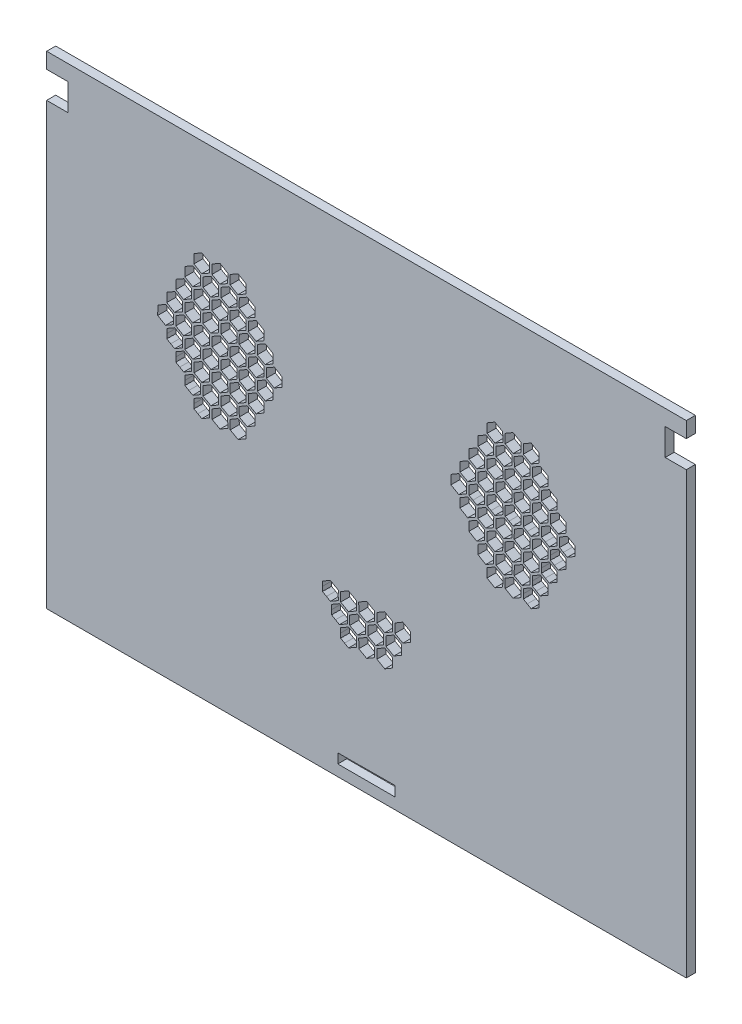
SolidWorks part; units mm, degrees
ref_plane "Front Plane" through (0, 0, 0) normal (0, 0, 1) x (1, 0, 0)
ref_plane "Top Plane" through (0, 0, 0) normal (0, 1, 0) x (1, 0, 0)
ref_plane "Right Plane" through (0, 0, 0) normal (1, 0, 0) x (0, 0, -1)
sketch "Sketch1" plane through (0, 0, 0) normal (0, 0, 1) x (1, 0, 0)
  line L0 (-106, 80) -> (-106, 74.8)
  line L1 (106, -80) -> (-106, -80)
  line L2 (106, -80) -> (106, 65.9)
  line L3 (106, 80) -> (-106, 80)
  line L4 (-106, -80) -> (-106, 65.9)
  line L5 (106, -80) -> (-106, 80) construction
  line L6 (106, 80) -> (-106, -80) construction
  line L8 (-106, 74.8) -> (-99, 74.8)
  line L10 (-106, 65.9) -> (-99, 65.9)
  line L11 (-99, 74.8) -> (-99, 65.9)
  line L12 (106, 65.9) -> (99, 65.9)
  line L13 (99, 74.8) -> (99, 65.9)
  line L14 (106, 74.8) -> (99, 74.8)
  line L15 (-106, 74.8) -> (-106, 80)
  line L16 (106, 74.8) -> (106, 80)
  line L18 (9.5, -73) -> (-9.5, -73.1166)
  line L19 (-2.0199, -73.1166) -> (-10.0199, -73.1166) construction
  line L20 (-9.5, -73.1166) -> (-9.5, -76.3166)
  line L21 (-9.5, -76.3166) -> (9.5, -76.3166)
  line L22 (9.5, -73) -> (9.5, -76.3166)
  line L275 (0, 24.0494) -> (50, 24.0494)
  line L276 (50, 24.0494) -> (-50, 24.0494)
  line L278 (0, 0) -> (0, 24.0494)
  line L284 (0, 24.0494) -> (-31.8655, 24.0494)
  line L290 (-31.8655, 24.0494) -> (31.8655, 24.0494)
  line L328 (-17.2944, 13.0523) -> (-57.2944, 43.241) construction
  line L337 (69.1585, 25.5708) -> (66.5481, 27.0493)
  line L354 (15.6596, 11.8186) -> (63.8404, 48.1814) construction
  line L355 (63.9873, 22.528) -> (66.5977, 21.0495)
  line L628 (-9.3462, -29.3321) -> (-9.371, -26.3322)
  line L629 (66.5977, 21.0495) -> (69.1833, 22.5709)
  line L630 (69.1833, 22.5709) -> (69.1585, 25.5708)
  line L631 (66.5481, 27.0493) -> (63.9625, 25.5279)
  line L632 (63.9625, 25.5279) -> (63.9873, 22.528)
  line L633 (57.9625, 25.5279) -> (57.9873, 22.528)
  line L638 (30, 4.0494) -> (70, 44.0494) construction
  line L639 (30, 44.0494) -> (70, 4.0494) construction
  line L640 (60.5481, 27.0493) -> (57.9625, 25.5279)
  line L641 (63.1585, 25.5708) -> (60.5481, 27.0493)
  line L642 (63.1833, 22.5709) -> (63.1585, 25.5708)
  line L643 (60.5977, 21.0495) -> (63.1833, 22.5709)
  line L644 (57.9873, 22.528) -> (60.5977, 21.0495)
  line L645 (51.9625, 25.5279) -> (51.9873, 22.528)
  line L646 (54.5481, 27.0493) -> (51.9625, 25.5279)
  line L647 (57.1585, 25.5708) -> (54.5481, 27.0493)
  line L648 (57.1833, 22.5709) -> (57.1585, 25.5708)
  line L649 (54.5977, 21.0495) -> (57.1833, 22.5709)
  line L650 (51.9873, 22.528) -> (54.5977, 21.0495)
  line L651 (45.9625, 25.5279) -> (45.9873, 22.528)
  line L652 (48.5481, 27.0493) -> (45.9625, 25.5279)
  line L653 (51.1585, 25.5708) -> (48.5481, 27.0493)
  line L654 (51.1833, 22.5709) -> (51.1585, 25.5708)
  line L655 (48.5977, 21.0495) -> (51.1833, 22.5709)
  line L656 (45.9873, 22.528) -> (48.5977, 21.0495)
  line L657 (39.9625, 25.5279) -> (39.9873, 22.528)
  line L658 (42.5481, 27.0493) -> (39.9625, 25.5279)
  line L659 (45.1585, 25.5708) -> (42.5481, 27.0493)
  line L660 (45.1833, 22.5709) -> (45.1585, 25.5708)
  line L661 (42.5977, 21.0495) -> (45.1833, 22.5709)
  line L662 (39.9873, 22.528) -> (42.5977, 21.0495)
  line L663 (33.9625, 25.5279) -> (33.9873, 22.528)
  line L664 (36.5481, 27.0493) -> (33.9625, 25.5279)
  line L665 (39.1585, 25.5708) -> (36.5481, 27.0493)
  line L666 (39.1833, 22.5709) -> (39.1585, 25.5708)
  line L667 (36.5977, 21.0495) -> (39.1833, 22.5709)
  line L668 (33.9873, 22.528) -> (36.5977, 21.0495)
  line L669 (27.9625, 25.5279) -> (27.9873, 22.528)
  line L670 (30.5481, 27.0493) -> (27.9625, 25.5279)
  line L671 (33.1585, 25.5708) -> (30.5481, 27.0493)
  line L672 (33.1833, 22.5709) -> (33.1585, 25.5708)
  line L673 (30.5977, 21.0495) -> (33.1833, 22.5709)
  line L674 (27.9873, 22.528) -> (30.5977, 21.0495)
  line L675 (60.9625, 30.7241) -> (60.9873, 27.7242)
  line L676 (63.5481, 32.2455) -> (60.9625, 30.7241)
  line L677 (66.1585, 30.767) -> (63.5481, 32.2455)
  line L678 (66.1833, 27.7671) -> (66.1585, 30.767)
  line L679 (63.5977, 26.2457) -> (66.1833, 27.7671)
  line L680 (60.9873, 27.7242) -> (63.5977, 26.2457)
  line L681 (57.9625, 35.9202) -> (57.9873, 32.9203)
  line L682 (60.5481, 37.4416) -> (57.9625, 35.9202)
  line L683 (63.1585, 35.9631) -> (60.5481, 37.4416)
  line L684 (63.1833, 32.9632) -> (63.1585, 35.9631)
  line L685 (60.5977, 31.4418) -> (63.1833, 32.9632)
  line L686 (57.9873, 32.9203) -> (60.5977, 31.4418)
  line L687 (54.9625, 41.1164) -> (54.9873, 38.1165)
  line L688 (57.5481, 42.6378) -> (54.9625, 41.1164)
  line L689 (60.1585, 41.1593) -> (57.5481, 42.6378)
  line L690 (60.1833, 38.1594) -> (60.1585, 41.1593)
  line L691 (57.5977, 36.638) -> (60.1833, 38.1594)
  line L692 (54.9873, 38.1165) -> (57.5977, 36.638)
  line L693 (60.9625, 20.3318) -> (60.9873, 17.3319)
  line L694 (63.5481, 21.8532) -> (60.9625, 20.3318)
  line L695 (66.1585, 20.3747) -> (63.5481, 21.8532)
  line L696 (66.1833, 17.3748) -> (66.1585, 20.3747)
  line L697 (63.5977, 15.8534) -> (66.1833, 17.3748)
  line L698 (60.9873, 17.3319) -> (63.5977, 15.8534)
  line L699 (57.9625, 15.1356) -> (57.9873, 12.1357)
  line L700 (60.5481, 16.657) -> (57.9625, 15.1356)
  line L701 (63.1585, 15.1785) -> (60.5481, 16.657)
  line L702 (63.1833, 12.1786) -> (63.1585, 15.1785)
  line L703 (60.5977, 10.6572) -> (63.1833, 12.1786)
  line L704 (57.9873, 12.1357) -> (60.5977, 10.6572)
  line L705 (54.9625, 9.9395) -> (54.9873, 6.9396)
  line L706 (57.5481, 11.4609) -> (54.9625, 9.9395)
  line L707 (60.1585, 9.9824) -> (57.5481, 11.4609)
  line L708 (60.1833, 6.9825) -> (60.1585, 9.9824)
  line L709 (57.5977, 5.4611) -> (60.1833, 6.9825)
  line L710 (54.9873, 6.9396) -> (57.5977, 5.4611)
  line L711 (51.9625, 4.7433) -> (51.9873, 1.7434)
  line L712 (54.5481, 6.2647) -> (51.9625, 4.7433)
  line L713 (57.1585, 4.7862) -> (54.5481, 6.2647)
  line L714 (57.1833, 1.7863) -> (57.1585, 4.7862)
  line L715 (54.5977, 0.2649) -> (57.1833, 1.7863)
  line L716 (51.9873, 1.7434) -> (54.5977, 0.2649)
  line L717 (60.9625, 30.7241) -> (60.9873, 27.7242)
  line L718 (63.5481, 32.2455) -> (60.9625, 30.7241)
  line L719 (66.1585, 30.767) -> (63.5481, 32.2455)
  line L720 (66.1833, 27.7671) -> (66.1585, 30.767)
  line L721 (63.5977, 26.2457) -> (66.1833, 27.7671)
  line L722 (60.9873, 27.7242) -> (63.5977, 26.2457)
  line L723 (57.9625, 35.9202) -> (57.9873, 32.9203)
  line L724 (60.5481, 37.4416) -> (57.9625, 35.9202)
  line L725 (63.1585, 35.9631) -> (60.5481, 37.4416)
  line L726 (63.1833, 32.9632) -> (63.1585, 35.9631)
  line L727 (60.5977, 31.4418) -> (63.1833, 32.9632)
  line L728 (57.9873, 32.9203) -> (60.5977, 31.4418)
  line L729 (54.9625, 41.1164) -> (54.9873, 38.1165)
  line L730 (57.5481, 42.6378) -> (54.9625, 41.1164)
  line L731 (60.1585, 41.1593) -> (57.5481, 42.6378)
  line L732 (60.1833, 38.1594) -> (60.1585, 41.1593)
  line L733 (57.5977, 36.638) -> (60.1833, 38.1594)
  line L734 (54.9873, 38.1165) -> (57.5977, 36.638)
  line L735 (51.9625, 46.3125) -> (51.9873, 43.3126)
  line L736 (54.5481, 47.8339) -> (51.9625, 46.3125)
  line L737 (57.1585, 46.3554) -> (54.5481, 47.8339)
  line L738 (57.1833, 43.3555) -> (57.1585, 46.3554)
  line L739 (54.5977, 41.8341) -> (57.1833, 43.3555)
  line L740 (51.9873, 43.3126) -> (54.5977, 41.8341)
  line L741 (57.5977, 26.2457) -> (60.1833, 27.7671)
  line L742 (54.9873, 27.7242) -> (57.5977, 26.2457)
  line L743 (54.9625, 30.7241) -> (54.9873, 27.7242)
  line L744 (57.5481, 32.2455) -> (54.9625, 30.7241)
  line L745 (60.1585, 30.767) -> (57.5481, 32.2455)
  line L746 (60.1833, 27.7671) -> (60.1585, 30.767)
  line L747 (51.5977, 26.2457) -> (54.1833, 27.7671)
  line L748 (48.9873, 27.7242) -> (51.5977, 26.2457)
  line L749 (48.9625, 30.7241) -> (48.9873, 27.7242)
  line L750 (51.5481, 32.2455) -> (48.9625, 30.7241)
  line L751 (54.1585, 30.767) -> (51.5481, 32.2455)
  line L752 (54.1833, 27.7671) -> (54.1585, 30.767)
  line L753 (45.5977, 26.2457) -> (48.1833, 27.7671)
  line L754 (42.9873, 27.7242) -> (45.5977, 26.2457)
  line L755 (42.9625, 30.7241) -> (42.9873, 27.7242)
  line L756 (45.5481, 32.2455) -> (42.9625, 30.7241)
  line L757 (48.1585, 30.767) -> (45.5481, 32.2455)
  line L758 (48.1833, 27.7671) -> (48.1585, 30.767)
  line L759 (39.5977, 26.2457) -> (42.1833, 27.7671)
  line L760 (36.9873, 27.7242) -> (39.5977, 26.2457)
  line L761 (36.9625, 30.7241) -> (36.9873, 27.7242)
  line L762 (39.5481, 32.2455) -> (36.9625, 30.7241)
  line L763 (42.1585, 30.767) -> (39.5481, 32.2455)
  line L764 (42.1833, 27.7671) -> (42.1585, 30.767)
  line L765 (33.5977, 26.2457) -> (36.1833, 27.7671)
  line L766 (30.9873, 27.7242) -> (33.5977, 26.2457)
  line L767 (30.9625, 30.7241) -> (30.9873, 27.7242)
  line L768 (33.5481, 32.2455) -> (30.9625, 30.7241)
  line L769 (36.1585, 30.767) -> (33.5481, 32.2455)
  line L770 (36.1833, 27.7671) -> (36.1585, 30.767)
  line L771 (57.5977, 26.2457) -> (60.1833, 27.7671)
  line L772 (54.9873, 27.7242) -> (57.5977, 26.2457)
  line L773 (54.9625, 30.7241) -> (54.9873, 27.7242)
  line L774 (57.5481, 32.2455) -> (54.9625, 30.7241)
  line L775 (60.1585, 30.767) -> (57.5481, 32.2455)
  line L776 (60.1833, 27.7671) -> (60.1585, 30.767)
  line L777 (54.5481, 37.4416) -> (51.9625, 35.9202)
  line L778 (51.9625, 35.9202) -> (51.9873, 32.9203)
  line L779 (51.9873, 32.9203) -> (54.5977, 31.4418)
  line L780 (54.5977, 31.4418) -> (57.1833, 32.9632)
  line L781 (57.1833, 32.9632) -> (57.1585, 35.9631)
  line L782 (57.1585, 35.9631) -> (54.5481, 37.4416)
  line L783 (48.9873, 38.1165) -> (51.5977, 36.638)
  line L784 (48.9625, 41.1164) -> (48.9873, 38.1165)
  line L785 (51.5481, 42.6378) -> (48.9625, 41.1164)
  line L786 (54.1585, 41.1593) -> (51.5481, 42.6378)
  line L787 (54.1833, 38.1594) -> (54.1585, 41.1593)
  line L788 (51.5977, 36.638) -> (54.1833, 38.1594)
  line L789 (45.9873, 43.3126) -> (48.5977, 41.8341)
  line L790 (45.9625, 46.3125) -> (45.9873, 43.3126)
  line L791 (48.5481, 47.8339) -> (45.9625, 46.3125)
  line L792 (51.1585, 46.3554) -> (48.5481, 47.8339)
  line L793 (51.1833, 43.3555) -> (51.1585, 46.3554)
  line L794 (48.5977, 41.8341) -> (51.1833, 43.3555)
  line L795 (51.5977, 26.2457) -> (54.1833, 27.7671)
  line L796 (48.9873, 27.7242) -> (51.5977, 26.2457)
  line L797 (48.9625, 30.7241) -> (48.9873, 27.7242)
  line L798 (51.5481, 32.2455) -> (48.9625, 30.7241)
  line L799 (54.1585, 30.767) -> (51.5481, 32.2455)
  line L800 (54.1833, 27.7671) -> (54.1585, 30.767)
  line L801 (48.5481, 37.4416) -> (45.9625, 35.9202)
  line L802 (45.9625, 35.9202) -> (45.9873, 32.9203)
  line L803 (45.9873, 32.9203) -> (48.5977, 31.4418)
  line L804 (48.5977, 31.4418) -> (51.1833, 32.9632)
  line L805 (51.1833, 32.9632) -> (51.1585, 35.9631)
  line L806 (51.1585, 35.9631) -> (48.5481, 37.4416)
  line L807 (42.9873, 38.1165) -> (45.5977, 36.638)
  line L808 (42.9625, 41.1164) -> (42.9873, 38.1165)
  line L809 (45.5481, 42.6378) -> (42.9625, 41.1164)
  line L810 (48.1585, 41.1593) -> (45.5481, 42.6378)
  line L811 (48.1833, 38.1594) -> (48.1585, 41.1593)
  line L812 (45.5977, 36.638) -> (48.1833, 38.1594)
  line L813 (39.9873, 43.3126) -> (42.5977, 41.8341)
  line L814 (39.9625, 46.3125) -> (39.9873, 43.3126)
  line L815 (42.5481, 47.8339) -> (39.9625, 46.3125)
  line L816 (45.1585, 46.3554) -> (42.5481, 47.8339)
  line L817 (45.1833, 43.3555) -> (45.1585, 46.3554)
  line L818 (42.5977, 41.8341) -> (45.1833, 43.3555)
  line L819 (45.5977, 26.2457) -> (48.1833, 27.7671)
  line L820 (42.9873, 27.7242) -> (45.5977, 26.2457)
  line L821 (42.9625, 30.7241) -> (42.9873, 27.7242)
  line L822 (45.5481, 32.2455) -> (42.9625, 30.7241)
  line L823 (48.1585, 30.767) -> (45.5481, 32.2455)
  line L824 (48.1833, 27.7671) -> (48.1585, 30.767)
  line L825 (42.5481, 37.4416) -> (39.9625, 35.9202)
  line L826 (39.9625, 35.9202) -> (39.9873, 32.9203)
  line L827 (39.9873, 32.9203) -> (42.5977, 31.4418)
  line L828 (42.5977, 31.4418) -> (45.1833, 32.9632)
  line L829 (45.1833, 32.9632) -> (45.1585, 35.9631)
  line L830 (45.1585, 35.9631) -> (42.5481, 37.4416)
  line L831 (36.9873, 38.1165) -> (39.5977, 36.638)
  line L832 (36.9625, 41.1164) -> (36.9873, 38.1165)
  line L833 (39.5481, 42.6378) -> (36.9625, 41.1164)
  line L834 (42.1585, 41.1593) -> (39.5481, 42.6378)
  line L835 (42.1833, 38.1594) -> (42.1585, 41.1593)
  line L836 (39.5977, 36.638) -> (42.1833, 38.1594)
  line L843 (39.5977, 26.2457) -> (42.1833, 27.7671)
  line L844 (36.9873, 27.7242) -> (39.5977, 26.2457)
  line L845 (36.9625, 30.7241) -> (36.9873, 27.7242)
  line L846 (39.5481, 32.2455) -> (36.9625, 30.7241)
  line L847 (42.1585, 30.767) -> (39.5481, 32.2455)
  line L848 (42.1833, 27.7671) -> (42.1585, 30.767)
  line L849 (36.5481, 37.4416) -> (33.9625, 35.9202)
  line L850 (33.9625, 35.9202) -> (33.9873, 32.9203)
  line L851 (33.9873, 32.9203) -> (36.5977, 31.4418)
  line L852 (36.5977, 31.4418) -> (39.1833, 32.9632)
  line L853 (39.1833, 32.9632) -> (39.1585, 35.9631)
  line L854 (39.1585, 35.9631) -> (36.5481, 37.4416)
  line L867 (33.9873, 43.3126) -> (36.5977, 41.8341) [skipped]
  line L868 (33.9625, 46.3125) -> (33.9873, 43.3126) [skipped]
  line L869 (36.5481, 47.8339) -> (33.9625, 46.3125) [skipped]
  line L870 (27.9873, 43.3126) -> (30.5977, 41.8341) [skipped]
  line L871 (27.9625, 46.3125) -> (27.9873, 43.3126) [skipped]
  line L872 (30.5481, 47.8339) -> (27.9625, 46.3125) [skipped]
  line L873 (33.1585, 46.3554) -> (30.5481, 47.8339) [skipped]
  line L874 (33.1833, 43.3555) -> (33.1585, 46.3554) [skipped]
  line L875 (30.5977, 41.8341) -> (33.1833, 43.3555) [skipped]
  line L876 (39.1585, 46.3554) -> (36.5481, 47.8339) [skipped]
  line L877 (36.5977, 41.8341) -> (39.1833, 43.3555) [skipped]
  line L878 (39.1833, 43.3555) -> (39.1585, 46.3554) [skipped]
  line L879 (36.1585, 41.1593) -> (33.5481, 42.6378) [skipped]
  line L880 (33.5481, 42.6378) -> (30.9625, 41.1164) [skipped]
  line L881 (30.9625, 41.1164) -> (30.9873, 38.1165) [skipped]
  line L882 (30.9873, 38.1165) -> (33.5977, 36.638) [skipped]
  line L883 (33.5977, 36.638) -> (36.1833, 38.1594) [skipped]
  line L884 (36.1833, 38.1594) -> (36.1585, 41.1593) [skipped]
  line L885 (39.1585, 12.1357) -> (36.5481, 10.6572)
  line L886 (39.1833, 15.1356) -> (39.1585, 12.1357)
  line L887 (36.5977, 16.657) -> (39.1833, 15.1356)
  line L888 (33.9873, 15.1785) -> (36.5977, 16.657)
  line L889 (33.9625, 12.1786) -> (33.9873, 15.1785)
  line L890 (36.5481, 10.6572) -> (33.9625, 12.1786)
  line L891 (42.1833, 20.3318) -> (42.1585, 17.3319)
  line L892 (42.1585, 17.3319) -> (39.5481, 15.8534)
  line L893 (39.5481, 15.8534) -> (36.9625, 17.3748)
  line L894 (36.9625, 17.3748) -> (36.9873, 20.3747)
  line L895 (36.9873, 20.3747) -> (39.5977, 21.8532)
  line L896 (39.5977, 21.8532) -> (42.1833, 20.3318)
  line L897 (39.5977, 11.4609) -> (42.1833, 9.9395)
  line L898 (42.1833, 9.9395) -> (42.1585, 6.9396)
  line L899 (42.1585, 6.9396) -> (39.5481, 5.4611)
  line L900 (39.5481, 5.4611) -> (36.9625, 6.9825)
  line L901 (36.9625, 6.9825) -> (36.9873, 9.9824)
  line L902 (36.9873, 9.9824) -> (39.5977, 11.4609)
  line L903 (45.1585, 12.1357) -> (42.5481, 10.6572)
  line L904 (45.1833, 15.1356) -> (45.1585, 12.1357)
  line L905 (42.5977, 16.657) -> (45.1833, 15.1356)
  line L906 (39.9873, 15.1785) -> (42.5977, 16.657)
  line L907 (39.9625, 12.1786) -> (39.9873, 15.1785)
  line L908 (42.5481, 10.6572) -> (39.9625, 12.1786)
  line L909 (48.1833, 20.3318) -> (48.1585, 17.3319)
  line L910 (48.1585, 17.3319) -> (45.5481, 15.8534)
  line L911 (45.5481, 15.8534) -> (42.9625, 17.3748)
  line L912 (42.9625, 17.3748) -> (42.9873, 20.3747)
  line L913 (42.9873, 20.3747) -> (45.5977, 21.8532)
  line L914 (45.5977, 21.8532) -> (48.1833, 20.3318)
  line L915 (42.5977, 6.2647) -> (45.1833, 4.7433)
  line L916 (45.1833, 4.7433) -> (45.1585, 1.7434)
  line L917 (45.1585, 1.7434) -> (42.5481, 0.2649)
  line L918 (42.5481, 0.2649) -> (39.9625, 1.7863)
  line L919 (39.9625, 1.7863) -> (39.9873, 4.7862)
  line L920 (39.9873, 4.7862) -> (42.5977, 6.2647)
  line L921 (45.5977, 11.4609) -> (48.1833, 9.9395)
  line L922 (48.1833, 9.9395) -> (48.1585, 6.9396)
  line L923 (48.1585, 6.9396) -> (45.5481, 5.4611)
  line L924 (45.5481, 5.4611) -> (42.9625, 6.9825)
  line L925 (42.9625, 6.9825) -> (42.9873, 9.9824)
  line L926 (42.9873, 9.9824) -> (45.5977, 11.4609)
  line L927 (51.1585, 12.1357) -> (48.5481, 10.6572)
  line L928 (51.1833, 15.1356) -> (51.1585, 12.1357)
  line L929 (48.5977, 16.657) -> (51.1833, 15.1356)
  line L930 (45.9873, 15.1785) -> (48.5977, 16.657)
  line L931 (45.9625, 12.1786) -> (45.9873, 15.1785)
  line L932 (48.5481, 10.6572) -> (45.9625, 12.1786)
  line L933 (54.1833, 20.3318) -> (54.1585, 17.3319)
  line L934 (54.1585, 17.3319) -> (51.5481, 15.8534)
  line L935 (51.5481, 15.8534) -> (48.9625, 17.3748)
  line L936 (48.9625, 17.3748) -> (48.9873, 20.3747)
  line L937 (48.9873, 20.3747) -> (51.5977, 21.8532)
  line L938 (51.5977, 21.8532) -> (54.1833, 20.3318)
  line L939 (48.5977, 6.2647) -> (51.1833, 4.7433)
  line L940 (51.1833, 4.7433) -> (51.1585, 1.7434)
  line L941 (51.1585, 1.7434) -> (48.5481, 0.2649)
  line L942 (48.5481, 0.2649) -> (45.9625, 1.7863)
  line L943 (45.9625, 1.7863) -> (45.9873, 4.7862)
  line L944 (45.9873, 4.7862) -> (48.5977, 6.2647)
  line L945 (51.5977, 11.4609) -> (54.1833, 9.9395)
  line L946 (54.1833, 9.9395) -> (54.1585, 6.9396)
  line L947 (54.1585, 6.9396) -> (51.5481, 5.4611)
  line L948 (51.5481, 5.4611) -> (48.9625, 6.9825)
  line L949 (48.9625, 6.9825) -> (48.9873, 9.9824)
  line L950 (48.9873, 9.9824) -> (51.5977, 11.4609)
  line L951 (57.1585, 12.1357) -> (54.5481, 10.6572)
  line L952 (57.1833, 15.1356) -> (57.1585, 12.1357)
  line L953 (54.5977, 16.657) -> (57.1833, 15.1356)
  line L954 (51.9873, 15.1785) -> (54.5977, 16.657)
  line L955 (51.9625, 12.1786) -> (51.9873, 15.1785)
  line L956 (54.5481, 10.6572) -> (51.9625, 12.1786)
  line L957 (60.1833, 20.3318) -> (60.1585, 17.3319)
  line L958 (60.1585, 17.3319) -> (57.5481, 15.8534)
  line L959 (57.5481, 15.8534) -> (54.9625, 17.3748)
  line L960 (54.9625, 17.3748) -> (54.9873, 20.3747)
  line L961 (54.9873, 20.3747) -> (57.5977, 21.8532)
  line L962 (57.5977, 21.8532) -> (60.1833, 20.3318)
  line L963 (36.1833, 20.3318) -> (36.1585, 17.3319)
  line L964 (36.1585, 17.3319) -> (33.5481, 15.8534)
  line L965 (33.5481, 15.8534) -> (30.9625, 17.3748)
  line L966 (30.9625, 17.3748) -> (30.9873, 20.3747)
  line L967 (30.9873, 20.3747) -> (33.5977, 21.8532)
  line L968 (33.5977, 21.8532) -> (36.1833, 20.3318)
  line L969 (42.1833, 20.3318) -> (42.1585, 17.3319)
  line L970 (42.1585, 17.3319) -> (39.5481, 15.8534)
  line L971 (39.5481, 15.8534) -> (36.9625, 17.3748)
  line L972 (36.9625, 17.3748) -> (36.9873, 20.3747)
  line L973 (36.9873, 20.3747) -> (39.5977, 21.8532)
  line L974 (39.5977, 21.8532) -> (42.1833, 20.3318)
  line L975 (48.1833, 20.3318) -> (48.1585, 17.3319)
  line L976 (48.1585, 17.3319) -> (45.5481, 15.8534)
  line L977 (45.5481, 15.8534) -> (42.9625, 17.3748)
  line L978 (42.9625, 17.3748) -> (42.9873, 20.3747)
  line L979 (42.9873, 20.3747) -> (45.5977, 21.8532)
  line L980 (45.5977, 21.8532) -> (48.1833, 20.3318)
  line L981 (54.1833, 20.3318) -> (54.1585, 17.3319)
  line L982 (54.1585, 17.3319) -> (51.5481, 15.8534)
  line L983 (51.5481, 15.8534) -> (48.9625, 17.3748)
  line L984 (48.9625, 17.3748) -> (48.9873, 20.3747)
  line L985 (48.9873, 20.3747) -> (51.5977, 21.8532)
  line L986 (51.5977, 21.8532) -> (54.1833, 20.3318)
  line L987 (60.1833, 20.3318) -> (60.1585, 17.3319)
  line L988 (60.1585, 17.3319) -> (57.5481, 15.8534)
  line L989 (57.5481, 15.8534) -> (54.9625, 17.3748)
  line L990 (54.9625, 17.3748) -> (54.9873, 20.3747)
  line L991 (54.9873, 20.3747) -> (57.5977, 21.8532)
  line L992 (57.5977, 21.8532) -> (60.1833, 20.3318)
  line L993 (51.9873, 4.7862) -> (54.5977, 6.2647)
  line L994 (54.5977, 6.2647) -> (57.1833, 4.7433)
  line L995 (57.1833, 4.7433) -> (57.1585, 1.7434)
  line L996 (57.1585, 1.7434) -> (54.5481, 0.2649)
  line L997 (54.5481, 0.2649) -> (51.9625, 1.7863)
  line L998 (51.9625, 1.7863) -> (51.9873, 4.7862)
  line L999 (54.9873, 9.9824) -> (57.5977, 11.4609)
  line L1000 (57.5977, 11.4609) -> (60.1833, 9.9395)
  line L1001 (60.1833, 9.9395) -> (60.1585, 6.9396)
  line L1002 (60.1585, 6.9396) -> (57.5481, 5.4611)
  line L1003 (57.5481, 5.4611) -> (54.9625, 6.9825)
  line L1004 (54.9625, 6.9825) -> (54.9873, 9.9824)
  line L1005 (57.9873, 15.1785) -> (60.5977, 16.657)
  line L1006 (60.5977, 16.657) -> (63.1833, 15.1356)
  line L1007 (63.1833, 15.1356) -> (63.1585, 12.1357)
  line L1008 (63.1585, 12.1357) -> (60.5481, 10.6572)
  line L1009 (60.5481, 10.6572) -> (57.9625, 12.1786)
  line L1010 (57.9625, 12.1786) -> (57.9873, 15.1785)
  line L1011 (60.9873, 20.3747) -> (63.5977, 21.8532)
  line L1012 (63.5977, 21.8532) -> (66.1833, 20.3318)
  line L1013 (66.1833, 20.3318) -> (66.1585, 17.3319)
  line L1014 (66.1585, 17.3319) -> (63.5481, 15.8534)
  line L1015 (63.5481, 15.8534) -> (60.9625, 17.3748)
  line L1016 (60.9625, 17.3748) -> (60.9873, 20.3747)
  line L1017 (54.9873, 9.9824) -> (57.5977, 11.4609)
  line L1018 (57.5977, 11.4609) -> (60.1833, 9.9395)
  line L1019 (60.1833, 9.9395) -> (60.1585, 6.9396)
  line L1020 (60.1585, 6.9396) -> (57.5481, 5.4611)
  line L1021 (57.5481, 5.4611) -> (54.9625, 6.9825)
  line L1022 (54.9625, 6.9825) -> (54.9873, 9.9824)
  line L1023 (57.9873, 15.1785) -> (60.5977, 16.657)
  line L1024 (60.5977, 16.657) -> (63.1833, 15.1356)
  line L1025 (63.1833, 15.1356) -> (63.1585, 12.1357)
  line L1026 (63.1585, 12.1357) -> (60.5481, 10.6572)
  line L1027 (60.5481, 10.6572) -> (57.9625, 12.1786)
  line L1028 (57.9625, 12.1786) -> (57.9873, 15.1785)
  line L1029 (60.9873, 20.3747) -> (63.5977, 21.8532)
  line L1030 (63.5977, 21.8532) -> (66.1833, 20.3318)
  line L1031 (66.1833, 20.3318) -> (66.1585, 17.3319)
  line L1032 (66.1585, 17.3319) -> (63.5481, 15.8534)
  line L1033 (63.5481, 15.8534) -> (60.9625, 17.3748)
  line L1034 (60.9625, 17.3748) -> (60.9873, 20.3747)
  line L1035 (33.1585, 22.528) -> (30.5481, 21.0495)
  line L1036 (39.1585, 22.528) -> (36.5481, 21.0495)
  line L1037 (36.5481, 21.0495) -> (33.9625, 22.5709)
  line L1038 (45.1585, 22.528) -> (42.5481, 21.0495)
  line L1039 (42.5481, 21.0495) -> (39.9625, 22.5709)
  line L1040 (51.1585, 22.528) -> (48.5481, 21.0495)
  line L1041 (48.5481, 21.0495) -> (45.9625, 22.5709)
  line L1042 (57.1585, 22.528) -> (54.5481, 21.0495)
  line L1043 (54.5481, 21.0495) -> (51.9625, 22.5709)
  line L1044 (63.1585, 22.528) -> (60.5481, 21.0495)
  line L1045 (60.5481, 21.0495) -> (57.9625, 22.5709)
  line L1046 (66.5481, 21.0495) -> (63.9625, 22.5709)
  line L1047 (69.1585, 22.528) -> (66.5481, 21.0495)
  line L1048 (-30, 44.0494) -> (-70, 4.0494) construction
  line L1049 (-30, 4.0494) -> (-70, 44.0494) construction
  line L1050 (-69.1585, 22.528) -> (-66.5481, 21.0495)
  line L1051 (-66.5481, 21.0495) -> (-63.9625, 22.5709)
  line L1052 (-60.5481, 21.0495) -> (-57.9625, 22.5709)
  line L1053 (-63.1585, 22.528) -> (-60.5481, 21.0495)
  line L1054 (-54.5481, 21.0495) -> (-51.9625, 22.5709)
  line L1055 (-57.1585, 22.528) -> (-54.5481, 21.0495)
  line L1056 (-48.5481, 21.0495) -> (-45.9625, 22.5709)
  line L1057 (-51.1585, 22.528) -> (-48.5481, 21.0495)
  line L1058 (-42.5481, 21.0495) -> (-39.9625, 22.5709)
  line L1059 (-45.1585, 22.528) -> (-42.5481, 21.0495)
  line L1060 (-36.5481, 21.0495) -> (-33.9625, 22.5709)
  line L1061 (-39.1585, 22.528) -> (-36.5481, 21.0495)
  line L1062 (-33.1585, 22.528) -> (-30.5481, 21.0495)
  line L1063 (-60.9625, 17.3748) -> (-60.9873, 20.3747)
  line L1064 (-63.5481, 15.8534) -> (-60.9625, 17.3748)
  line L1065 (-66.1585, 17.3319) -> (-63.5481, 15.8534)
  line L1066 (-66.1833, 20.3318) -> (-66.1585, 17.3319)
  line L1067 (-63.5977, 21.8532) -> (-66.1833, 20.3318)
  line L1068 (-60.9873, 20.3747) -> (-63.5977, 21.8532)
  line L1069 (-57.9625, 12.1786) -> (-57.9873, 15.1785)
  line L1070 (-60.5481, 10.6572) -> (-57.9625, 12.1786)
  line L1071 (-63.1585, 12.1357) -> (-60.5481, 10.6572)
  line L1072 (-63.1833, 15.1356) -> (-63.1585, 12.1357)
  line L1073 (-60.5977, 16.657) -> (-63.1833, 15.1356)
  line L1074 (-57.9873, 15.1785) -> (-60.5977, 16.657)
  line L1075 (-54.9625, 6.9825) -> (-54.9873, 9.9824)
  line L1076 (-57.5481, 5.4611) -> (-54.9625, 6.9825)
  line L1077 (-60.1585, 6.9396) -> (-57.5481, 5.4611)
  line L1078 (-60.1833, 9.9395) -> (-60.1585, 6.9396)
  line L1079 (-57.5977, 11.4609) -> (-60.1833, 9.9395)
  line L1080 (-54.9873, 9.9824) -> (-57.5977, 11.4609)
  line L1081 (-60.9625, 17.3748) -> (-60.9873, 20.3747)
  line L1082 (-63.5481, 15.8534) -> (-60.9625, 17.3748)
  line L1083 (-66.1585, 17.3319) -> (-63.5481, 15.8534)
  line L1084 (-66.1833, 20.3318) -> (-66.1585, 17.3319)
  line L1085 (-63.5977, 21.8532) -> (-66.1833, 20.3318)
  line L1086 (-60.9873, 20.3747) -> (-63.5977, 21.8532)
  line L1087 (-57.9625, 12.1786) -> (-57.9873, 15.1785)
  line L1088 (-60.5481, 10.6572) -> (-57.9625, 12.1786)
  line L1089 (-63.1585, 12.1357) -> (-60.5481, 10.6572)
  line L1090 (-63.1833, 15.1356) -> (-63.1585, 12.1357)
  line L1091 (-60.5977, 16.657) -> (-63.1833, 15.1356)
  line L1092 (-57.9873, 15.1785) -> (-60.5977, 16.657)
  line L1093 (-54.9625, 6.9825) -> (-54.9873, 9.9824)
  line L1094 (-57.5481, 5.4611) -> (-54.9625, 6.9825)
  line L1095 (-60.1585, 6.9396) -> (-57.5481, 5.4611)
  line L1096 (-60.1833, 9.9395) -> (-60.1585, 6.9396)
  line L1097 (-57.5977, 11.4609) -> (-60.1833, 9.9395)
  line L1098 (-54.9873, 9.9824) -> (-57.5977, 11.4609)
  line L1099 (-51.9625, 1.7863) -> (-51.9873, 4.7862)
  line L1100 (-54.5481, 0.2649) -> (-51.9625, 1.7863)
  line L1101 (-57.1585, 1.7434) -> (-54.5481, 0.2649)
  line L1102 (-57.1833, 4.7433) -> (-57.1585, 1.7434)
  line L1103 (-54.5977, 6.2647) -> (-57.1833, 4.7433)
  line L1104 (-51.9873, 4.7862) -> (-54.5977, 6.2647)
  line L1105 (-57.5977, 21.8532) -> (-60.1833, 20.3318)
  line L1106 (-54.9873, 20.3747) -> (-57.5977, 21.8532)
  line L1107 (-54.9625, 17.3748) -> (-54.9873, 20.3747)
  line L1108 (-57.5481, 15.8534) -> (-54.9625, 17.3748)
  line L1109 (-60.1585, 17.3319) -> (-57.5481, 15.8534)
  line L1110 (-60.1833, 20.3318) -> (-60.1585, 17.3319)
  line L1111 (-51.5977, 21.8532) -> (-54.1833, 20.3318)
  line L1112 (-48.9873, 20.3747) -> (-51.5977, 21.8532)
  line L1113 (-48.9625, 17.3748) -> (-48.9873, 20.3747)
  line L1114 (-51.5481, 15.8534) -> (-48.9625, 17.3748)
  line L1115 (-54.1585, 17.3319) -> (-51.5481, 15.8534)
  line L1116 (-54.1833, 20.3318) -> (-54.1585, 17.3319)
  line L1117 (-45.5977, 21.8532) -> (-48.1833, 20.3318)
  line L1118 (-42.9873, 20.3747) -> (-45.5977, 21.8532)
  line L1119 (-42.9625, 17.3748) -> (-42.9873, 20.3747)
  line L1120 (-45.5481, 15.8534) -> (-42.9625, 17.3748)
  line L1121 (-48.1585, 17.3319) -> (-45.5481, 15.8534)
  line L1122 (-48.1833, 20.3318) -> (-48.1585, 17.3319)
  line L1123 (-39.5977, 21.8532) -> (-42.1833, 20.3318)
  line L1124 (-36.9873, 20.3747) -> (-39.5977, 21.8532)
  line L1125 (-36.9625, 17.3748) -> (-36.9873, 20.3747)
  line L1126 (-39.5481, 15.8534) -> (-36.9625, 17.3748)
  line L1127 (-42.1585, 17.3319) -> (-39.5481, 15.8534)
  line L1128 (-42.1833, 20.3318) -> (-42.1585, 17.3319)
  line L1129 (-33.5977, 21.8532) -> (-36.1833, 20.3318)
  line L1130 (-30.9873, 20.3747) -> (-33.5977, 21.8532)
  line L1131 (-30.9625, 17.3748) -> (-30.9873, 20.3747)
  line L1132 (-33.5481, 15.8534) -> (-30.9625, 17.3748)
  line L1133 (-36.1585, 17.3319) -> (-33.5481, 15.8534)
  line L1134 (-36.1833, 20.3318) -> (-36.1585, 17.3319)
  line L1135 (-57.5977, 21.8532) -> (-60.1833, 20.3318)
  line L1136 (-54.9873, 20.3747) -> (-57.5977, 21.8532)
  line L1137 (-54.9625, 17.3748) -> (-54.9873, 20.3747)
  line L1138 (-57.5481, 15.8534) -> (-54.9625, 17.3748)
  line L1139 (-60.1585, 17.3319) -> (-57.5481, 15.8534)
  line L1140 (-60.1833, 20.3318) -> (-60.1585, 17.3319)
  line L1141 (-54.5481, 10.6572) -> (-51.9625, 12.1786)
  line L1142 (-51.9625, 12.1786) -> (-51.9873, 15.1785)
  line L1143 (-51.9873, 15.1785) -> (-54.5977, 16.657)
  line L1144 (-54.5977, 16.657) -> (-57.1833, 15.1356)
  line L1145 (-57.1833, 15.1356) -> (-57.1585, 12.1357)
  line L1146 (-57.1585, 12.1357) -> (-54.5481, 10.6572)
  line L1147 (-48.9873, 9.9824) -> (-51.5977, 11.4609)
  line L1148 (-48.9625, 6.9825) -> (-48.9873, 9.9824)
  line L1149 (-51.5481, 5.4611) -> (-48.9625, 6.9825)
  line L1150 (-54.1585, 6.9396) -> (-51.5481, 5.4611)
  line L1151 (-54.1833, 9.9395) -> (-54.1585, 6.9396)
  line L1152 (-51.5977, 11.4609) -> (-54.1833, 9.9395)
  line L1153 (-45.9873, 4.7862) -> (-48.5977, 6.2647)
  line L1154 (-45.9625, 1.7863) -> (-45.9873, 4.7862)
  line L1155 (-48.5481, 0.2649) -> (-45.9625, 1.7863)
  line L1156 (-51.1585, 1.7434) -> (-48.5481, 0.2649)
  line L1157 (-51.1833, 4.7433) -> (-51.1585, 1.7434)
  line L1158 (-48.5977, 6.2647) -> (-51.1833, 4.7433)
  line L1159 (-51.5977, 21.8532) -> (-54.1833, 20.3318)
  line L1160 (-48.9873, 20.3747) -> (-51.5977, 21.8532)
  line L1161 (-48.9625, 17.3748) -> (-48.9873, 20.3747)
  line L1162 (-51.5481, 15.8534) -> (-48.9625, 17.3748)
  line L1163 (-54.1585, 17.3319) -> (-51.5481, 15.8534)
  line L1164 (-54.1833, 20.3318) -> (-54.1585, 17.3319)
  line L1165 (-48.5481, 10.6572) -> (-45.9625, 12.1786)
  line L1166 (-45.9625, 12.1786) -> (-45.9873, 15.1785)
  line L1167 (-45.9873, 15.1785) -> (-48.5977, 16.657)
  line L1168 (-48.5977, 16.657) -> (-51.1833, 15.1356)
  line L1169 (-51.1833, 15.1356) -> (-51.1585, 12.1357)
  line L1170 (-51.1585, 12.1357) -> (-48.5481, 10.6572)
  line L1171 (-42.9873, 9.9824) -> (-45.5977, 11.4609)
  line L1172 (-42.9625, 6.9825) -> (-42.9873, 9.9824)
  line L1173 (-45.5481, 5.4611) -> (-42.9625, 6.9825)
  line L1174 (-48.1585, 6.9396) -> (-45.5481, 5.4611)
  line L1175 (-48.1833, 9.9395) -> (-48.1585, 6.9396)
  line L1176 (-45.5977, 11.4609) -> (-48.1833, 9.9395)
  line L1177 (-39.9873, 4.7862) -> (-42.5977, 6.2647)
  line L1178 (-39.9625, 1.7863) -> (-39.9873, 4.7862)
  line L1179 (-42.5481, 0.2649) -> (-39.9625, 1.7863)
  line L1180 (-45.1585, 1.7434) -> (-42.5481, 0.2649)
  line L1181 (-45.1833, 4.7433) -> (-45.1585, 1.7434)
  line L1182 (-42.5977, 6.2647) -> (-45.1833, 4.7433)
  line L1183 (-45.5977, 21.8532) -> (-48.1833, 20.3318)
  line L1184 (-42.9873, 20.3747) -> (-45.5977, 21.8532)
  line L1185 (-42.9625, 17.3748) -> (-42.9873, 20.3747)
  line L1186 (-45.5481, 15.8534) -> (-42.9625, 17.3748)
  line L1187 (-48.1585, 17.3319) -> (-45.5481, 15.8534)
  line L1188 (-48.1833, 20.3318) -> (-48.1585, 17.3319)
  line L1189 (-42.5481, 10.6572) -> (-39.9625, 12.1786)
  line L1190 (-39.9625, 12.1786) -> (-39.9873, 15.1785)
  line L1191 (-39.9873, 15.1785) -> (-42.5977, 16.657)
  line L1192 (-42.5977, 16.657) -> (-45.1833, 15.1356)
  line L1193 (-45.1833, 15.1356) -> (-45.1585, 12.1357)
  line L1194 (-45.1585, 12.1357) -> (-42.5481, 10.6572)
  line L1195 (-36.9873, 9.9824) -> (-39.5977, 11.4609)
  line L1196 (-36.9625, 6.9825) -> (-36.9873, 9.9824)
  line L1197 (-39.5481, 5.4611) -> (-36.9625, 6.9825)
  line L1198 (-42.1585, 6.9396) -> (-39.5481, 5.4611)
  line L1199 (-42.1833, 9.9395) -> (-42.1585, 6.9396)
  line L1200 (-39.5977, 11.4609) -> (-42.1833, 9.9395)
  line L1201 (-39.5977, 21.8532) -> (-42.1833, 20.3318)
  line L1202 (-36.9873, 20.3747) -> (-39.5977, 21.8532)
  line L1203 (-36.9625, 17.3748) -> (-36.9873, 20.3747)
  line L1204 (-39.5481, 15.8534) -> (-36.9625, 17.3748)
  line L1205 (-42.1585, 17.3319) -> (-39.5481, 15.8534)
  line L1206 (-42.1833, 20.3318) -> (-42.1585, 17.3319)
  line L1207 (-36.5481, 10.6572) -> (-33.9625, 12.1786)
  line L1208 (-33.9625, 12.1786) -> (-33.9873, 15.1785)
  line L1209 (-33.9873, 15.1785) -> (-36.5977, 16.657)
  line L1210 (-36.5977, 16.657) -> (-39.1833, 15.1356)
  line L1211 (-39.1833, 15.1356) -> (-39.1585, 12.1357)
  line L1212 (-39.1585, 12.1357) -> (-36.5481, 10.6572)
  line L1213 (-39.1585, 35.9631) -> (-36.5481, 37.4416)
  line L1214 (-39.1833, 32.9632) -> (-39.1585, 35.9631)
  line L1215 (-36.5977, 31.4418) -> (-39.1833, 32.9632)
  line L1216 (-33.9873, 32.9203) -> (-36.5977, 31.4418)
  line L1217 (-33.9625, 35.9202) -> (-33.9873, 32.9203)
  line L1218 (-36.5481, 37.4416) -> (-33.9625, 35.9202)
  line L1219 (-42.1833, 27.7671) -> (-42.1585, 30.767)
  line L1220 (-42.1585, 30.767) -> (-39.5481, 32.2455)
  line L1221 (-39.5481, 32.2455) -> (-36.9625, 30.7241)
  line L1222 (-36.9625, 30.7241) -> (-36.9873, 27.7242)
  line L1223 (-36.9873, 27.7242) -> (-39.5977, 26.2457)
  line L1224 (-39.5977, 26.2457) -> (-42.1833, 27.7671)
  line L1225 (-39.5977, 36.638) -> (-42.1833, 38.1594)
  line L1226 (-42.1833, 38.1594) -> (-42.1585, 41.1593)
  line L1227 (-42.1585, 41.1593) -> (-39.5481, 42.6378)
  line L1228 (-39.5481, 42.6378) -> (-36.9625, 41.1164)
  line L1229 (-36.9625, 41.1164) -> (-36.9873, 38.1165)
  line L1230 (-36.9873, 38.1165) -> (-39.5977, 36.638)
  line L1231 (-45.1585, 35.9631) -> (-42.5481, 37.4416)
  line L1232 (-45.1833, 32.9632) -> (-45.1585, 35.9631)
  line L1233 (-42.5977, 31.4418) -> (-45.1833, 32.9632)
  line L1234 (-39.9873, 32.9203) -> (-42.5977, 31.4418)
  line L1235 (-39.9625, 35.9202) -> (-39.9873, 32.9203)
  line L1236 (-42.5481, 37.4416) -> (-39.9625, 35.9202)
  line L1237 (-48.1833, 27.7671) -> (-48.1585, 30.767)
  line L1238 (-48.1585, 30.767) -> (-45.5481, 32.2455)
  line L1239 (-45.5481, 32.2455) -> (-42.9625, 30.7241)
  line L1240 (-42.9625, 30.7241) -> (-42.9873, 27.7242)
  line L1241 (-42.9873, 27.7242) -> (-45.5977, 26.2457)
  line L1242 (-45.5977, 26.2457) -> (-48.1833, 27.7671)
  line L1243 (-42.5977, 41.8341) -> (-45.1833, 43.3555)
  line L1244 (-45.1833, 43.3555) -> (-45.1585, 46.3554)
  line L1245 (-45.1585, 46.3554) -> (-42.5481, 47.8339)
  line L1246 (-42.5481, 47.8339) -> (-39.9625, 46.3125)
  line L1247 (-39.9625, 46.3125) -> (-39.9873, 43.3126)
  line L1248 (-39.9873, 43.3126) -> (-42.5977, 41.8341)
  line L1249 (-45.5977, 36.638) -> (-48.1833, 38.1594)
  line L1250 (-48.1833, 38.1594) -> (-48.1585, 41.1593)
  line L1251 (-48.1585, 41.1593) -> (-45.5481, 42.6378)
  line L1252 (-45.5481, 42.6378) -> (-42.9625, 41.1164)
  line L1253 (-42.9625, 41.1164) -> (-42.9873, 38.1165)
  line L1254 (-42.9873, 38.1165) -> (-45.5977, 36.638)
  line L1255 (-51.1585, 35.9631) -> (-48.5481, 37.4416)
  line L1256 (-51.1833, 32.9632) -> (-51.1585, 35.9631)
  line L1257 (-48.5977, 31.4418) -> (-51.1833, 32.9632)
  line L1258 (-45.9873, 32.9203) -> (-48.5977, 31.4418)
  line L1259 (-45.9625, 35.9202) -> (-45.9873, 32.9203)
  line L1260 (-48.5481, 37.4416) -> (-45.9625, 35.9202)
  line L1261 (-54.1833, 27.7671) -> (-54.1585, 30.767)
  line L1262 (-54.1585, 30.767) -> (-51.5481, 32.2455)
  line L1263 (-51.5481, 32.2455) -> (-48.9625, 30.7241)
  line L1264 (-48.9625, 30.7241) -> (-48.9873, 27.7242)
  line L1265 (-48.9873, 27.7242) -> (-51.5977, 26.2457)
  line L1266 (-51.5977, 26.2457) -> (-54.1833, 27.7671)
  line L1267 (-48.5977, 41.8341) -> (-51.1833, 43.3555)
  line L1268 (-51.1833, 43.3555) -> (-51.1585, 46.3554)
  line L1269 (-51.1585, 46.3554) -> (-48.5481, 47.8339)
  line L1270 (-48.5481, 47.8339) -> (-45.9625, 46.3125)
  line L1271 (-45.9625, 46.3125) -> (-45.9873, 43.3126)
  line L1272 (-45.9873, 43.3126) -> (-48.5977, 41.8341)
  line L1273 (-51.5977, 36.638) -> (-54.1833, 38.1594)
  line L1274 (-54.1833, 38.1594) -> (-54.1585, 41.1593)
  line L1275 (-54.1585, 41.1593) -> (-51.5481, 42.6378)
  line L1276 (-51.5481, 42.6378) -> (-48.9625, 41.1164)
  line L1277 (-48.9625, 41.1164) -> (-48.9873, 38.1165)
  line L1278 (-48.9873, 38.1165) -> (-51.5977, 36.638)
  line L1279 (-57.1585, 35.9631) -> (-54.5481, 37.4416)
  line L1280 (-57.1833, 32.9632) -> (-57.1585, 35.9631)
  line L1281 (-54.5977, 31.4418) -> (-57.1833, 32.9632)
  line L1282 (-51.9873, 32.9203) -> (-54.5977, 31.4418)
  line L1283 (-51.9625, 35.9202) -> (-51.9873, 32.9203)
  line L1284 (-54.5481, 37.4416) -> (-51.9625, 35.9202)
  line L1285 (-60.1833, 27.7671) -> (-60.1585, 30.767)
  line L1286 (-60.1585, 30.767) -> (-57.5481, 32.2455)
  line L1287 (-57.5481, 32.2455) -> (-54.9625, 30.7241)
  line L1288 (-54.9625, 30.7241) -> (-54.9873, 27.7242)
  line L1289 (-54.9873, 27.7242) -> (-57.5977, 26.2457)
  line L1290 (-57.5977, 26.2457) -> (-60.1833, 27.7671)
  line L1291 (-36.1833, 27.7671) -> (-36.1585, 30.767)
  line L1292 (-36.1585, 30.767) -> (-33.5481, 32.2455)
  line L1293 (-33.5481, 32.2455) -> (-30.9625, 30.7241)
  line L1294 (-30.9625, 30.7241) -> (-30.9873, 27.7242)
  line L1295 (-30.9873, 27.7242) -> (-33.5977, 26.2457)
  line L1296 (-33.5977, 26.2457) -> (-36.1833, 27.7671)
  line L1297 (-42.1833, 27.7671) -> (-42.1585, 30.767)
  line L1298 (-42.1585, 30.767) -> (-39.5481, 32.2455)
  line L1299 (-39.5481, 32.2455) -> (-36.9625, 30.7241)
  line L1300 (-36.9625, 30.7241) -> (-36.9873, 27.7242)
  line L1301 (-36.9873, 27.7242) -> (-39.5977, 26.2457)
  line L1302 (-39.5977, 26.2457) -> (-42.1833, 27.7671)
  line L1303 (-48.1833, 27.7671) -> (-48.1585, 30.767)
  line L1304 (-48.1585, 30.767) -> (-45.5481, 32.2455)
  line L1305 (-45.5481, 32.2455) -> (-42.9625, 30.7241)
  line L1306 (-42.9625, 30.7241) -> (-42.9873, 27.7242)
  line L1307 (-42.9873, 27.7242) -> (-45.5977, 26.2457)
  line L1308 (-45.5977, 26.2457) -> (-48.1833, 27.7671)
  line L1309 (-54.1833, 27.7671) -> (-54.1585, 30.767)
  line L1310 (-54.1585, 30.767) -> (-51.5481, 32.2455)
  line L1311 (-51.5481, 32.2455) -> (-48.9625, 30.7241)
  line L1312 (-48.9625, 30.7241) -> (-48.9873, 27.7242)
  line L1313 (-48.9873, 27.7242) -> (-51.5977, 26.2457)
  line L1314 (-51.5977, 26.2457) -> (-54.1833, 27.7671)
  line L1315 (-60.1833, 27.7671) -> (-60.1585, 30.767)
  line L1316 (-60.1585, 30.767) -> (-57.5481, 32.2455)
  line L1317 (-57.5481, 32.2455) -> (-54.9625, 30.7241)
  line L1318 (-54.9625, 30.7241) -> (-54.9873, 27.7242)
  line L1319 (-54.9873, 27.7242) -> (-57.5977, 26.2457)
  line L1320 (-57.5977, 26.2457) -> (-60.1833, 27.7671)
  line L1321 (-51.9873, 43.3126) -> (-54.5977, 41.8341)
  line L1322 (-54.5977, 41.8341) -> (-57.1833, 43.3555)
  line L1323 (-57.1833, 43.3555) -> (-57.1585, 46.3554)
  line L1324 (-57.1585, 46.3554) -> (-54.5481, 47.8339)
  line L1325 (-54.5481, 47.8339) -> (-51.9625, 46.3125)
  line L1326 (-51.9625, 46.3125) -> (-51.9873, 43.3126)
  line L1327 (-54.9873, 38.1165) -> (-57.5977, 36.638)
  line L1328 (-57.5977, 36.638) -> (-60.1833, 38.1594)
  line L1329 (-60.1833, 38.1594) -> (-60.1585, 41.1593)
  line L1330 (-60.1585, 41.1593) -> (-57.5481, 42.6378)
  line L1331 (-57.5481, 42.6378) -> (-54.9625, 41.1164)
  line L1332 (-54.9625, 41.1164) -> (-54.9873, 38.1165)
  line L1333 (-57.9873, 32.9203) -> (-60.5977, 31.4418)
  line L1334 (-60.5977, 31.4418) -> (-63.1833, 32.9632)
  line L1335 (-63.1833, 32.9632) -> (-63.1585, 35.9631)
  line L1336 (-63.1585, 35.9631) -> (-60.5481, 37.4416)
  line L1337 (-60.5481, 37.4416) -> (-57.9625, 35.9202)
  line L1338 (-57.9625, 35.9202) -> (-57.9873, 32.9203)
  line L1339 (-60.9873, 27.7242) -> (-63.5977, 26.2457)
  line L1340 (-63.5977, 26.2457) -> (-66.1833, 27.7671)
  line L1341 (-66.1833, 27.7671) -> (-66.1585, 30.767)
  line L1342 (-66.1585, 30.767) -> (-63.5481, 32.2455)
  line L1343 (-63.5481, 32.2455) -> (-60.9625, 30.7241)
  line L1344 (-60.9625, 30.7241) -> (-60.9873, 27.7242)
  line L1345 (-51.9873, 1.7434) -> (-54.5977, 0.2649)
  line L1346 (-54.5977, 0.2649) -> (-57.1833, 1.7863)
  line L1347 (-57.1833, 1.7863) -> (-57.1585, 4.7862)
  line L1348 (-57.1585, 4.7862) -> (-54.5481, 6.2647)
  line L1349 (-54.5481, 6.2647) -> (-51.9625, 4.7433)
  line L1350 (-51.9625, 4.7433) -> (-51.9873, 1.7434)
  line L1351 (-54.9873, 6.9396) -> (-57.5977, 5.4611)
  line L1352 (-57.5977, 5.4611) -> (-60.1833, 6.9825)
  line L1353 (-60.1833, 6.9825) -> (-60.1585, 9.9824)
  line L1354 (-60.1585, 9.9824) -> (-57.5481, 11.4609)
  line L1355 (-57.5481, 11.4609) -> (-54.9625, 9.9395)
  line L1356 (-54.9625, 9.9395) -> (-54.9873, 6.9396)
  line L1357 (-57.9873, 12.1357) -> (-60.5977, 10.6572)
  line L1358 (-60.5977, 10.6572) -> (-63.1833, 12.1786)
  line L1359 (-63.1833, 12.1786) -> (-63.1585, 15.1785)
  line L1360 (-63.1585, 15.1785) -> (-60.5481, 16.657)
  line L1361 (-60.5481, 16.657) -> (-57.9625, 15.1356)
  line L1362 (-57.9625, 15.1356) -> (-57.9873, 12.1357)
  line L1363 (-60.9873, 17.3319) -> (-63.5977, 15.8534)
  line L1364 (-63.5977, 15.8534) -> (-66.1833, 17.3748)
  line L1365 (-66.1833, 17.3748) -> (-66.1585, 20.3747)
  line L1366 (-66.1585, 20.3747) -> (-63.5481, 21.8532)
  line L1367 (-63.5481, 21.8532) -> (-60.9625, 20.3318)
  line L1368 (-60.9625, 20.3318) -> (-60.9873, 17.3319)
  line L1369 (-54.9873, 38.1165) -> (-57.5977, 36.638)
  line L1370 (-57.5977, 36.638) -> (-60.1833, 38.1594)
  line L1371 (-60.1833, 38.1594) -> (-60.1585, 41.1593)
  line L1372 (-60.1585, 41.1593) -> (-57.5481, 42.6378)
  line L1373 (-57.5481, 42.6378) -> (-54.9625, 41.1164)
  line L1374 (-54.9625, 41.1164) -> (-54.9873, 38.1165)
  line L1375 (-57.9873, 32.9203) -> (-60.5977, 31.4418)
  line L1376 (-60.5977, 31.4418) -> (-63.1833, 32.9632)
  line L1377 (-63.1833, 32.9632) -> (-63.1585, 35.9631)
  line L1378 (-63.1585, 35.9631) -> (-60.5481, 37.4416)
  line L1379 (-60.5481, 37.4416) -> (-57.9625, 35.9202)
  line L1380 (-57.9625, 35.9202) -> (-57.9873, 32.9203)
  line L1381 (-60.9873, 27.7242) -> (-63.5977, 26.2457)
  line L1382 (-63.5977, 26.2457) -> (-66.1833, 27.7671)
  line L1383 (-66.1833, 27.7671) -> (-66.1585, 30.767)
  line L1384 (-66.1585, 30.767) -> (-63.5481, 32.2455)
  line L1385 (-63.5481, 32.2455) -> (-60.9625, 30.7241)
  line L1386 (-60.9625, 30.7241) -> (-60.9873, 27.7242)
  line L1387 (-27.9873, 22.528) -> (-30.5977, 21.0495)
  line L1388 (-30.5977, 21.0495) -> (-33.1833, 22.5709)
  line L1389 (-33.1833, 22.5709) -> (-33.1585, 25.5708)
  line L1390 (-33.1585, 25.5708) -> (-30.5481, 27.0493)
  line L1391 (-30.5481, 27.0493) -> (-27.9625, 25.5279)
  line L1392 (-27.9625, 25.5279) -> (-27.9873, 22.528)
  line L1393 (-33.9873, 22.528) -> (-36.5977, 21.0495)
  line L1394 (-36.5977, 21.0495) -> (-39.1833, 22.5709)
  line L1395 (-39.1833, 22.5709) -> (-39.1585, 25.5708)
  line L1396 (-39.1585, 25.5708) -> (-36.5481, 27.0493)
  line L1397 (-36.5481, 27.0493) -> (-33.9625, 25.5279)
  line L1398 (-33.9625, 25.5279) -> (-33.9873, 22.528)
  line L1399 (-39.9873, 22.528) -> (-42.5977, 21.0495)
  line L1400 (-42.5977, 21.0495) -> (-45.1833, 22.5709)
  line L1401 (-45.1833, 22.5709) -> (-45.1585, 25.5708)
  line L1402 (-45.1585, 25.5708) -> (-42.5481, 27.0493)
  line L1403 (-42.5481, 27.0493) -> (-39.9625, 25.5279)
  line L1404 (-39.9625, 25.5279) -> (-39.9873, 22.528)
  line L1405 (-45.9873, 22.528) -> (-48.5977, 21.0495)
  line L1406 (-48.5977, 21.0495) -> (-51.1833, 22.5709)
  line L1407 (-51.1833, 22.5709) -> (-51.1585, 25.5708)
  line L1408 (-51.1585, 25.5708) -> (-48.5481, 27.0493)
  line L1409 (-48.5481, 27.0493) -> (-45.9625, 25.5279)
  line L1410 (-45.9625, 25.5279) -> (-45.9873, 22.528)
  line L1411 (-51.9873, 22.528) -> (-54.5977, 21.0495)
  line L1412 (-54.5977, 21.0495) -> (-57.1833, 22.5709)
  line L1413 (-57.1833, 22.5709) -> (-57.1585, 25.5708)
  line L1414 (-57.1585, 25.5708) -> (-54.5481, 27.0493)
  line L1415 (-54.5481, 27.0493) -> (-51.9625, 25.5279)
  line L1416 (-51.9625, 25.5279) -> (-51.9873, 22.528)
  line L1417 (-57.9873, 22.528) -> (-60.5977, 21.0495)
  line L1418 (-60.5977, 21.0495) -> (-63.1833, 22.5709)
  line L1419 (-63.1833, 22.5709) -> (-63.1585, 25.5708)
  line L1420 (-63.1585, 25.5708) -> (-60.5481, 27.0493)
  line L1421 (-60.5481, 27.0493) -> (-57.9625, 25.5279)
  line L1426 (-57.9625, 25.5279) -> (-57.9873, 22.528)
  line L1427 (-63.9625, 25.5279) -> (-63.9873, 22.528)
  line L1428 (-66.5481, 27.0493) -> (-63.9625, 25.5279)
  line L1429 (-69.1833, 22.5709) -> (-69.1585, 25.5708)
  line L1430 (-66.5977, 21.0495) -> (-69.1833, 22.5709)
  line L1431 (-63.9873, 22.528) -> (-66.5977, 21.0495)
  line L1432 (-69.1585, 25.5708) -> (-66.5481, 27.0493)
  line L1433 (-11.9318, -30.8535) -> (-9.3462, -29.3321)
  line L1434 (-14.5422, -29.375) -> (-11.9318, -30.8535)
  line L1435 (-14.5669, -26.3751) -> (-14.5422, -29.375)
  line L1436 (-11.9814, -24.8537) -> (-14.5669, -26.3751)
  line L1437 (-9.371, -26.3322) -> (-11.9814, -24.8537)
  line L1438 (-6.3462, -34.5282) -> (-6.371, -31.5283)
  line L1439 (-8.9318, -36.0496) -> (-6.3462, -34.5282)
  line L1440 (-11.5422, -34.5711) -> (-8.9318, -36.0496)
  line L1441 (-11.5669, -31.5713) -> (-11.5422, -34.5711)
  line L1442 (-8.9814, -30.0498) -> (-11.5669, -31.5713)
  line L1443 (-6.371, -31.5283) -> (-8.9814, -30.0498)
  line L1444 (-9.3462, -29.3321) -> (-9.371, -26.3322)
  line L1445 (-11.9318, -30.8535) -> (-9.3462, -29.3321)
  line L1446 (-14.5422, -29.375) -> (-11.9318, -30.8535)
  line L1447 (-14.5669, -26.3751) -> (-14.5422, -29.375)
  line L1448 (-11.9814, -24.8537) -> (-14.5669, -26.3751)
  line L1449 (-9.371, -26.3322) -> (-11.9814, -24.8537)
  line L1450 (-6.3462, -34.5282) -> (-6.371, -31.5283)
  line L1451 (-8.9318, -36.0496) -> (-6.3462, -34.5282)
  line L1452 (-11.5422, -34.5711) -> (-8.9318, -36.0496)
  line L1453 (-11.5669, -31.5713) -> (-11.5422, -34.5711)
  line L1454 (-8.9814, -30.0498) -> (-11.5669, -31.5713)
  line L1455 (-6.371, -31.5283) -> (-8.9814, -30.0498)
  line L1456 (-3.3462, -39.7244) -> (-3.371, -36.7245)
  line L1457 (-5.9318, -41.2458) -> (-3.3462, -39.7244)
  line L1458 (-8.5422, -39.7673) -> (-5.9318, -41.2458)
  line L1459 (-8.5669, -36.7674) -> (-8.5422, -39.7673)
  line L1460 (-5.9814, -35.246) -> (-8.5669, -36.7674)
  line L1461 (-3.371, -36.7245) -> (-5.9814, -35.246)
  line L1462 (-5.9318, -30.8535) -> (-3.3462, -29.3321)
  line L1463 (-3.3462, -29.3321) -> (-3.371, -26.3322)
  line L1464 (-3.371, -26.3322) -> (-5.9814, -24.8537)
  line L1465 (-5.9814, -24.8537) -> (-8.5669, -26.3751)
  line L1466 (-8.5669, -26.3751) -> (-8.5422, -29.375)
  line L1467 (-8.5422, -29.375) -> (-5.9318, -30.8535)
  line L1468 (-0.371, -31.5283) -> (-2.9814, -30.0498)
  line L1469 (-0.3462, -34.5282) -> (-0.371, -31.5283)
  line L1470 (-2.9318, -36.0496) -> (-0.3462, -34.5282)
  line L1471 (-5.5422, -34.5711) -> (-2.9318, -36.0496)
  line L1472 (-5.5669, -31.5713) -> (-5.5422, -34.5711)
  line L1473 (-2.9814, -30.0498) -> (-5.5669, -31.5713)
  line L1474 (2.629, -36.7245) -> (0.0186, -35.246)
  line L1475 (2.6538, -39.7244) -> (2.629, -36.7245)
  line L1476 (0.0682, -41.2458) -> (2.6538, -39.7244)
  line L1477 (-2.5422, -39.7673) -> (0.0682, -41.2458)
  line L1478 (-2.5669, -36.7674) -> (-2.5422, -39.7673)
  line L1479 (0.0186, -35.246) -> (-2.5669, -36.7674)
  line L1480 (0.0682, -30.8535) -> (2.6538, -29.3321)
  line L1481 (2.6538, -29.3321) -> (2.629, -26.3322)
  line L1482 (2.629, -26.3322) -> (0.0186, -24.8537)
  line L1483 (0.0186, -24.8537) -> (-2.5669, -26.3751)
  line L1484 (-2.5669, -26.3751) -> (-2.5422, -29.375)
  line L1485 (-2.5422, -29.375) -> (0.0682, -30.8535)
  line L1486 (5.629, -31.5283) -> (3.0186, -30.0498)
  line L1487 (5.6538, -34.5282) -> (5.629, -31.5283)
  line L1488 (3.0682, -36.0496) -> (5.6538, -34.5282)
  line L1489 (0.4578, -34.5711) -> (3.0682, -36.0496)
  line L1490 (0.4331, -31.5713) -> (0.4578, -34.5711)
  line L1491 (3.0186, -30.0498) -> (0.4331, -31.5713)
  line L1492 (8.629, -36.7245) -> (6.0186, -35.246)
  line L1493 (8.6538, -39.7244) -> (8.629, -36.7245)
  line L1494 (6.0682, -41.2458) -> (8.6538, -39.7244)
  line L1495 (3.4578, -39.7673) -> (6.0682, -41.2458)
  line L1496 (3.4331, -36.7674) -> (3.4578, -39.7673)
  line L1497 (6.0186, -35.246) -> (3.4331, -36.7674)
  line L1498 (6.0682, -30.8535) -> (8.6538, -29.3321)
  line L1499 (8.6538, -29.3321) -> (8.629, -26.3322)
  line L1500 (8.629, -26.3322) -> (6.0186, -24.8537)
  line L1501 (6.0186, -24.8537) -> (3.4331, -26.3751)
  line L1502 (3.4331, -26.3751) -> (3.4578, -29.375)
  line L1503 (3.4578, -29.375) -> (6.0682, -30.8535)
  line L1504 (11.629, -31.5283) -> (9.0186, -30.0498)
  line L1505 (11.6538, -34.5282) -> (11.629, -31.5283)
  line L1506 (9.0682, -36.0496) -> (11.6538, -34.5282)
  line L1507 (6.4578, -34.5711) -> (9.0682, -36.0496)
  line L1508 (6.4331, -31.5713) -> (6.4578, -34.5711)
  line L1509 (9.0186, -30.0498) -> (6.4331, -31.5713)
  line L1510 (12.0682, -30.8535) -> (14.6538, -29.3321)
  line L1511 (14.6538, -29.3321) -> (14.629, -26.3322)
  line L1512 (14.629, -26.3322) -> (12.0186, -24.8537)
  line L1513 (12.0186, -24.8537) -> (9.4331, -26.3751)
  line L1514 (9.4331, -26.3751) -> (9.4578, -29.375)
  line L1515 (9.4578, -29.375) -> (12.0682, -30.8535)
  line L1516 (-3.371, -39.7673) -> (-5.9814, -41.2458)
  line L1517 (-5.9814, -41.2458) -> (-8.5669, -39.7244)
  line L1518 (-8.5669, -39.7244) -> (-8.5422, -36.7245)
  line L1519 (-8.5422, -36.7245) -> (-5.9318, -35.246)
  line L1520 (-5.9318, -35.246) -> (-3.3462, -36.7674)
  line L1521 (-3.3462, -36.7674) -> (-3.371, -39.7673)
  line L1522 (-6.371, -34.5711) -> (-8.9814, -36.0496)
  line L1523 (-8.9814, -36.0496) -> (-11.5669, -34.5282)
  line L1524 (-11.5669, -34.5282) -> (-11.5422, -31.5283)
  line L1525 (-11.5422, -31.5283) -> (-8.9318, -30.0498)
  line L1526 (-8.9318, -30.0498) -> (-6.3462, -31.5713)
  line L1527 (-6.3462, -31.5713) -> (-6.371, -34.5711)
  line L1528 (-9.371, -29.375) -> (-11.9814, -30.8535)
  line L1529 (-11.9814, -30.8535) -> (-14.5669, -29.3321)
  line L1530 (-14.5669, -29.3321) -> (-14.5422, -26.3322)
  line L1531 (-14.5422, -26.3322) -> (-11.9318, -24.8537)
  line L1532 (-11.9318, -24.8537) -> (-9.3462, -26.3751)
  line L1533 (-9.3462, -26.3751) -> (-9.371, -29.375)
  line L1534 (0, 0) -> (0, -68.8823)
  circle A0 centre (66.5729, 24.0494) radius 3 construction
  circle A1 centre (-66.5729, 24.0494) radius 3 construction
  point P0 (0, 0)
  point P24 (0, -76.3166)
  dimension "D10" = 6
  dimension "D1" = 212
  dimension "D2" = 160
  dimension "D3" = 5.2
  dimension "D4" = 7
  dimension "D5" = 8.9
  dimension "D6" = 50
  dimension "D7" = 3.2
  dimension "D8" = 100
  dimension "D9" = 9.5
  dimension "D11" = 40
  dimension "D12" = 40
  dimension "D13" = 4
  dimension "D14" = 5
  dimension "D15" = 5
extrude "Boss-Extrude1" add sketch "Sketch1" along normal blind 3 contours L14 L16 L3 L0 L8 L11 L10 L4 L1 L2 L12 L13
